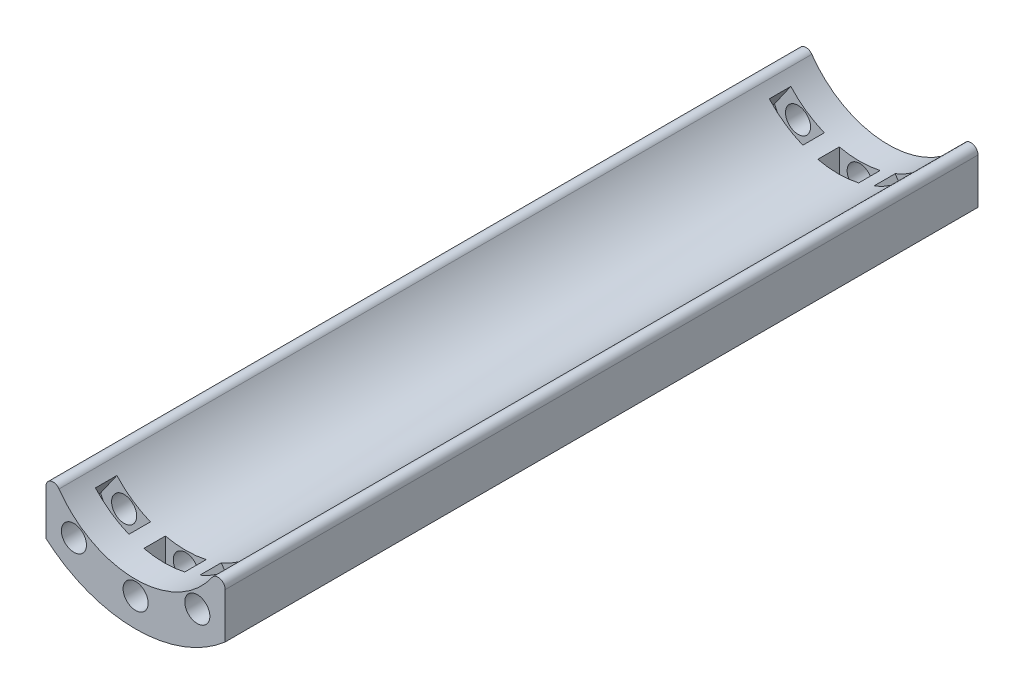
SolidWorks part; units mm, degrees
ref_plane "Front Plane" through (0, 0, 0) normal (0, 0, 1) x (1, 0, 0)
ref_plane "Top Plane" through (0, 0, 0) normal (0, 1, 0) x (1, 0, 0)
ref_plane "Right Plane" through (0, 0, 0) normal (1, 0, 0) x (0, 0, -1)
sketch "Sketch1" plane through (0, 0, 0) normal (0, 0, 1) x (1, 0, 0)
  line L2 (-18.375, -14.3091) -> (-18.375, 161.3091)
  line L3 (-43.375, 161.3091) -> (-43.375, 118.5)
  line L4 (-18.375, -14.3091) -> (-18.375, 161.3091)
  line L5 (-43.375, 161.3091) -> (-43.375, 118.5)
  line L78 (-25.375, 28.5) -> (-43.375, 28.5)
  line L79 (-25.375, 28.5) -> (-43.375, 28.5)
  line L80 (-43.375, 28.5) -> (-43.375, -14.3091)
  line L81 (-43.375, 28.5) -> (-43.375, -14.3091)
  line L82 (-43.375, 118.5) -> (-25.375, 118.5)
  line L83 (-43.375, 118.5) -> (-25.375, 118.5)
  line L84 (-25.375, 118.5) -> (-25.375, 28.5)
  line L85 (-25.375, 118.5) -> (-25.375, 28.5)
  circle A0 centre (-30.875, 0) radius 13
  arc A2 (-18.375, 161.3091) -> (-43.375, 161.3091) centre (-30.875, 147) ccw
  arc A3 (-43.375, -14.3091) -> (-18.375, -14.3091) centre (-30.875, 0) ccw
  arc A4 (-18.375, 161.3091) -> (-43.375, 161.3091) centre (-30.875, 147) ccw
  arc A5 (-43.375, -14.3091) -> (-18.375, -14.3091) centre (-30.875, 0) ccw
  dimension "D2" = 6
  dimension "D1" = 0
extrude "Boss-Extrude1" add sketch "Sketch1" along normal up to surface (105 mm away) contours L5 A5 L4 A0 region at (-30.875, -13.7148, 0)
sketch "Sketch3" plane through (0, 0, 0) normal (0, 0, -1) x (-1, 0, 0)
  circle A1 centre (30.875, -15) radius 1.75 construction
  circle A2 centre (39.4786, -12.2873) radius 1.75 construction
  circle A3 centre (22.2714, -12.2873) radius 1.75
  circle A4 centre (30.875, -15) radius 1.75
  circle A5 centre (39.4786, -12.2873) radius 1.75
  circle A6 centre (22.2714, -12.2873) radius 1.75 construction
  circle A7 centre (22.2714, -12.2873) radius 1.75 construction
extrude "Cut-Extrude1" cut sketch "Sketch3" against normal blind 15 contours A3 | A4 | A5 region at (-22.2714, -12.2873, 0) region at (-30.875, -15, 0) region at (-39.4786, -12.2873, 0)
ref_plane "Plane1" through (0, 0, 4) normal (0, 0, -1) x (-1, 0, 0)
ref_plane "Plane2" through (0, 0, 52.5) normal (0, 0, -1) x (-1, 0, 0)
sketch "Sketch4" plane through (0, 0, 4) normal (0, 0, -1) x (-1, 0, 0)
  line L0 (20.8806, -9.3047) -> (21.2653, -8.7552)
  line L1 (30.875, -18.2909) -> (33.725, -16.6454)
  line L2 (33.725, -16.6454) -> (33.725, -13.3546)
  line L3 (33.725, -13.3546) -> (30.875, -11.7091)
  line L4 (30.875, -11.7091) -> (28.025, -13.3546)
  line L5 (28.025, -13.3546) -> (28.025, -16.6454)
  line L6 (28.025, -16.6454) -> (30.875, -18.2909)
  line L7 (25.5497, -12.5741) -> (25.9345, -12.0246)
  line L8 (24.1589, -9.5915) -> (20.3838, -14.983) construction
  line L9 (20.3838, -14.983) -> (23.6621, -15.2698)
  line L10 (23.6621, -15.2698) -> (25.5497, -12.5741)
  line L11 (25.5497, -12.5741) -> (24.1589, -9.5915)
  line L12 (24.1589, -9.5915) -> (20.8806, -9.3047)
  line L13 (20.8806, -9.3047) -> (18.993, -12.0005)
  line L14 (18.993, -12.0005) -> (20.3838, -14.983)
  line L15 (30.875, 0) -> (24.1589, -9.5915) construction
  line L16 (30.875, 0) -> (30.875, -19) construction
  line L17 (28.025, -13.3546) -> (28.025, -12.6837)
  line L18 (33.725, -13.3546) -> (33.725, -12.6837)
  line L19 (36.2003, -12.5741) -> (37.5911, -9.5915)
  line L20 (37.5911, -9.5915) -> (40.8694, -9.3047)
  line L21 (40.8694, -9.3047) -> (42.757, -12.0005)
  line L22 (42.757, -12.0005) -> (41.3662, -14.983)
  line L23 (41.3662, -14.983) -> (38.0879, -15.2698)
  line L24 (38.0879, -15.2698) -> (36.2003, -12.5741)
  line L25 (36.2003, -12.5741) -> (35.8155, -12.0246)
  line L26 (40.8694, -9.3047) -> (40.4847, -8.7552)
  line L27 (18.375, -14.3091) -> (18.375, -3.5707) construction
  line L28 (18.375, -14.3091) -> (18.375, -3.5707)
  line L30 (43.375, -3.5707) -> (43.375, -14.3091)
  circle A0 centre (30.875, -15) radius 2.85 construction
  arc A1 (18.375, -14.3091) -> (43.375, -14.3091) centre (30.875, 0) ccw construction
  arc A2 (18.375, -14.3091) -> (43.375, -14.3091) centre (30.875, 0) ccw
  arc A3 (18.375, -3.5707) -> (43.375, -3.5707) centre (30.875, 0) ccw construction
  arc A4 (18.375, -3.5707) -> (43.375, -3.5707) centre (30.875, 0) ccw
  circle A5 centre (22.2714, -12.2873) radius 2.85 construction
  circle A6 centre (22.2714, -12.2873) radius 1.75 construction
  circle A7 centre (30.875, -15) radius 1.75 construction
  dimension "D1" = 5.7
extrude "Cut-Extrude2" cut sketch "Sketch4" against normal blind 3 contours A4 L12 L13 L14 A2 L9 L10 L11 | A4 L0 L12 | A4 L11 L7 | A4 L4 L5 L6 A2 L1 L2 L3 | A4 L17 L4 | A4 L3 L18 | A4 L19 L24 L23 A2 L22 L21 L20 | A4 L25 L19 | A4 L20 L26 region at (-21.3409, -9.1521, 4) region at (-22.1244, -12.4971, 4) region at (-25.5357, -12.0894, 4) region at (-28.3145, -12.9655, 4) region at (-30.875, -15.2561, 4) region at (-40.4091, -9.1521, 4) region at (-33.4355, -12.9655, 4) region at (-39.6256, -12.4971, 4) region at (-36.2143, -12.0894, 4)
mirror "Mirror1" about plane through (0, 0, 52.5) normal (0, 0, -1) of "Cut-Extrude1", "Cut-Extrude2"
fillet "Fillet1" radius 1 2 edges at (-18.375, -3.5707, 52.5) (-43.375, -3.5707, 52.5)
ref_plane "Plane3" through (0, -19, 0) normal (0, -1, 0) x (-1, 0, 0)
